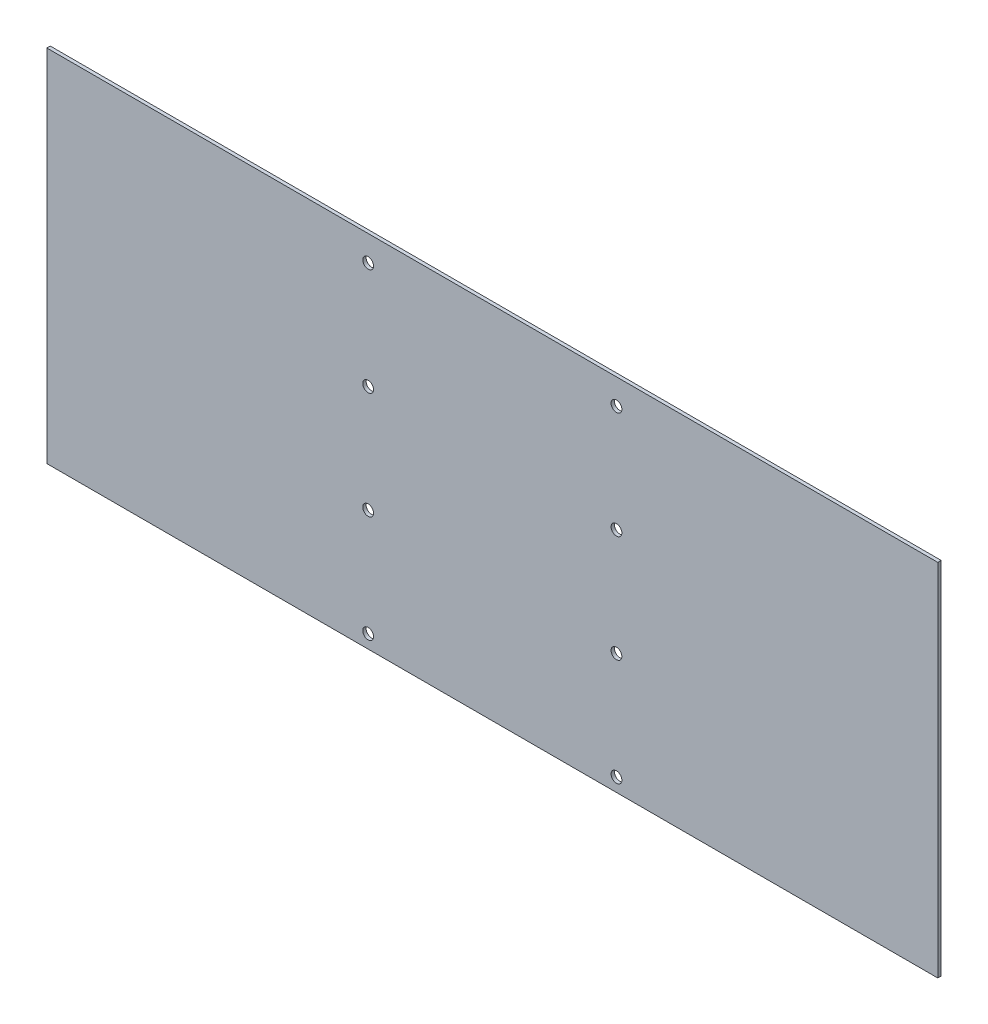
SolidWorks part; units mm, degrees
material "AISI 1020 Acero laminado en frío"
ref_plane "Alzado" through (0, 0, 0) normal (0, 0, 1) x (1, 0, 0)
ref_plane "Planta" through (0, 0, 0) normal (0, 1, 0) x (1, 0, 0)
ref_plane "Vista lateral" through (0, 0, 0) normal (1, 0, 0) x (0, 0, -1)
sketch "Croquis1" plane through (0, 0, 0) normal (0, 0, 1) x (1, 0, 0)
  line L1 (-340.9286, 201.5365) -> (491.4714, 201.5365)
  line L2 (-340.9286, 201.5365) -> (-340.9286, -134.7635)
  line L3 (-340.9286, -134.7635) -> (491.4714, -134.7635)
  line L4 (491.4714, 201.5365) -> (491.4714, -134.7635)
  dimension "D1" = 832.4
  dimension "D2" = 336.3
base flange "Brida base1" sketch "Croquis1" thickness 3.175 reverse thickness direction no parameters "D1"=0.7366
hole_wizard "Taladro de margen para 3/81" positions "Croquis3" profile "Croquis2" hole size "3/8" standard "Ansi Inch" end condition through all
sketch "Croquis3" plane through (0, 0, 0) normal (0, 0, 1) x (1, 0, 0)
  line L0 (-40.7286, 77.7365) -> (191.2714, 77.7365) construction
  line L5 (-40.7286, 77.7365) -> (-40.7286, -22.2635) construction
  line L7 (75.2714, 201.5365) -> (75.2714, 77.7365) construction
  line L8 (491.4714, 201.5365) -> (-340.9286, 201.5365) construction
  point P0 (-40.7286, 77.7365)
  point P2 (-40.7286, -22.2635)
  point P4 (191.2714, 77.7365)
  point P6 (191.2714, -22.2635)
  point P37 (-40.7286, -122.2635)
  point P39 (191.2714, -122.2635)
  point P41 (191.2714, 177.7365)
  point P43 (-40.7286, 177.7365)
  dimension "D1" = 232
  dimension "D2" = 100
  dimension "D3" = 123.8
  dimension "D4" = 100
  dimension "D5" = 100
sketch "Croquis2" plane through (-40.7286, 77.7365, 0) normal (1, 0, 0) x (0, -1, 0)
  line L0 (0, 0) -> (0, 3.175)
  line L1 (0, 3.175) -> (5.0419, 3.175)
  line L2 (5.0419, 3.175) -> (5.0419, 0)
  line L5 (5.0419, 0) -> (0, 0)
  line L11 (0, -6.35) -> (0, 107.95) construction
  dimension "Diámetro de taladro hasta el siguiente" = 10.0838
  dimension "Profundidad de taladro hasta el siguiente" = 3.175
sketch "Líneas de pliegue1" [suppressed] plane through (0, 0, 0) normal (0, 1, 0) x (1, 0, 0)
sketch "Cuadro delimitador1" [suppressed] plane through (0, 0, 0) normal (0, 1, 0) x (1, 0, 0)
sheet metal parameters "Chapa metálica1" thickness 3.175 parameters "D1"=0.7366
flat pattern "Chapa desplegada1" [suppressed]
sketch "Líneas de pliegue2" plane through (0, 0, 0) normal (0, 1, 0) x (1, 0, 0)
sketch3d "Cuadro delimitador2" [suppressed]
  line L0 (340.9286, -134.7635, 0) -> (-491.4714, -134.7635, 0) construction
  line L1 (340.9286, 201.5365, 0) -> (-491.4714, 201.5365, 0) construction
  line L2 (340.9286, -134.7635, 0) -> (340.9286, 201.5365, 0) construction
  line L3 (-491.4714, -134.7635, 0) -> (-491.4714, 201.5365, 0) construction
sheet metal parameters "Chapa metálica2" thickness 3.175 parameters "D1"=0.7366
flat pattern "Chapa desplegada1"
sketch "Líneas de pliegue2" plane through (0, 0, 0) normal (0, 1, 0) x (1, 0, 0)
sketch3d "Cuadro delimitador2" [suppressed]
  line L0 (-340.9286, -134.7635, 0) -> (491.4714, -134.7635, 0) construction
  line L1 (-340.9286, 201.5365, 0) -> (491.4714, 201.5365, 0) construction
  line L2 (-340.9286, -134.7635, 0) -> (-340.9286, 201.5365, 0) construction
  line L3 (491.4714, -134.7635, 0) -> (491.4714, 201.5365, 0) construction
